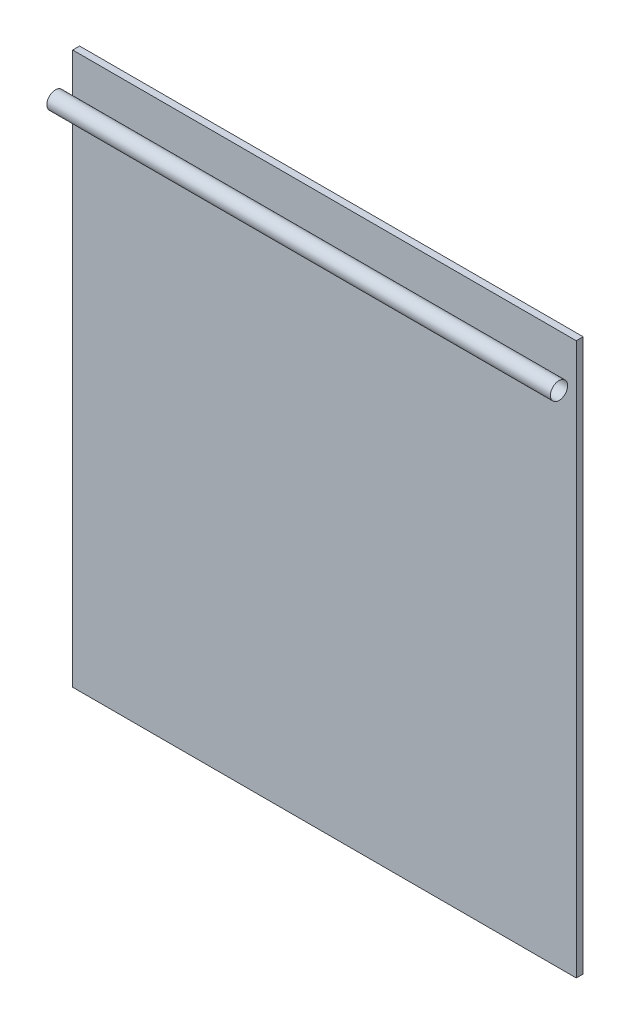
SolidWorks part; units mm, degrees
material "201 Annealed Stainless Steel (SS)"
ref_plane "Front Plane" through (0, 0, 0) normal (0, 0, 1) x (1, 0, 0)
ref_plane "Top Plane" through (0, 0, 0) normal (0, 1, 0) x (1, 0, 0)
ref_plane "Right Plane" through (0, 0, 0) normal (1, 0, 0) x (0, 0, -1)
sketch "Sketch1" plane through (0, 0, 0) normal (0, 0, 1) x (1, 0, 0)
  line L1 (-73, -80) -> (73, -80)
  line L2 (-73, -80) -> (-73, 80)
  line L3 (-73, 80) -> (73, 80)
  line L4 (73, -80) -> (73, 80)
  line L5 (-73, -80) -> (73, 80) construction
  line L6 (-73, 80) -> (73, -80) construction
  point P0 (0, 0)
  dimension "D1" = 146
  dimension "D2" = 160
extrude "Boss-Extrude1" add sketch "Sketch1" along normal blind 2
sketch "Sketch2" [suppressed] plane through (0, 0, 0) normal (0, 0, -1) x (-1, 0, 0)
  line L0 (61, 200) -> (61, -200) construction
  line L1 (-61, 314.7216) -> (-204.3993, 314.7216)
  line L2 (-61, 314.7216) -> (-61, -251.9618)
  line L3 (-61, -251.9618) -> (-204.3993, -251.9618)
  line L4 (-204.3993, 314.7216) -> (-204.3993, -251.9618)
  line L6 (61, 279.3211) -> (244.4765, 279.3211)
  line L7 (61, 279.3211) -> (61, -295.1839)
  line L8 (61, -295.1839) -> (244.4765, -295.1839)
  line L9 (244.4765, 279.3211) -> (244.4765, -295.1839)
  line L10 (-61, -200) -> (-61, -140) construction
  dimension "D1" = 122
extrude "Cut-Extrude1" [suppressed] cut sketch "Sketch2" against normal through all
sketch "Sketch3" plane through (73, 0, 0) normal (1, 0, 0) x (0, 0, -1)
  line L0 (-2, 80) -> (0, 80) construction
  line L1 (-2, 80) -> (-2, -80) construction
  circle A0 centre (-7, 70) radius 2.5
  point P2 (-7.932, 72.0042)
  dimension "D3" = 5
  dimension "D1" = 10
  dimension "D2" = 5
surface "Surface-Extrude1" sketch "Sketch3"
sketch "Sketch4" plane through (-73, 0, 0) normal (-1, 0, 0) x (0, 0, 1)
  line L1 (2, 80) -> (0, 80) construction
  line L2 (0, -80) -> (0, 80) construction
  point P0 (7.5, 76)
  dimension "D1" = 4
  dimension "D2" = 7.5
ref_axis "Axis1" through (-73, 76, 7.5) along (1, 0, 0)
sketch "Sketch5" [suppressed] plane through (0, 0, 0) normal (0, 0, -1) x (-1, 0, 0)
  line L0 (49, 80) -> (49, -80) construction
  line L1 (-49, 80) -> (49, 80)
  line L2 (-49, 80) -> (-49, 60.2594)
  line L3 (-49, 60.2594) -> (49, 60.2594)
  line L4 (49, 80) -> (49, 60.2594)
extrude "Cut-Extrude2" [suppressed] cut sketch "Sketch5" against normal blind 3
sketch "Sketch6" [suppressed] plane through (0, 0, 2) normal (0, 0, 1) x (1, 0, 0)
  line L0 (0, 0) -> (103.2002, 0) construction
  line L1 (-40, 80) -> (-40, 108.3319) construction
  line L2 (-40, 80) -> (-27.987, 80) construction
  line L3 (0, 0) -> (0, 138.3235) construction
  line L4 (40, 80) -> (27.987, 80) construction
  line L5 (40, 80) -> (40, 108.3319) construction
  line L6 (40, -80) -> (40, -108.3319) construction
  line L7 (40, -80) -> (27.987, -80) construction
  line L8 (-40, -80) -> (-27.987, -80) construction
  line L9 (-40, -80) -> (-40, -108.3319) construction
  circle A0 centre (-40, 80) radius 4.5
  circle A2 centre (-45.8, 85.8) radius 1.95
  circle A3 centre (-45.8, 74.2) radius 1.95
  circle A4 centre (-34.2, 74.2) radius 1.95
  circle A5 centre (-34.2, 85.8) radius 1.95
  circle A6 centre (34.2, 85.8) radius 1.95
  circle A7 centre (34.2, 74.2) radius 1.95
  circle A8 centre (45.8, 74.2) radius 1.95
  circle A9 centre (45.8, 85.8) radius 1.95
  circle A10 centre (40, 80) radius 4.5
  circle A11 centre (40, -80) radius 4.5
  circle A12 centre (45.8, -85.8) radius 1.95
  circle A13 centre (45.8, -74.2) radius 1.95
  circle A14 centre (34.2, -74.2) radius 1.95
  circle A15 centre (34.2, -85.8) radius 1.95
  circle A16 centre (-34.2, -85.8) radius 1.95
  circle A17 centre (-34.2, -74.2) radius 1.95
  circle A18 centre (-45.8, -74.2) radius 1.95
  circle A19 centre (-45.8, -85.8) radius 1.95
  circle A20 centre (-40, -80) radius 4.5
  circle A21 centre (-40, 80) radius 5.1 construction
  dimension "D1" = 9
  dimension "D3" = 3.9
extrude "Leandut_holes" [suppressed] cut sketch "Sketch6" against normal through all
chamfer "Chamfer1" [suppressed] distance 5 angle 45
sketch "Sketch7" plane through (0, 0, 2) normal (0, 0, 1) x (1, 0, 0)
  line L0 (73, 80) -> (-73, 80) construction
  line L1 (-23, -125) -> (23, -125)
  line L2 (-23, -125) -> (-23, 60)
  line L3 (-23, 60) -> (23, 60)
  line L4 (23, -125) -> (23, 60)
  line L5 (0, 0) -> (0, -66.8576) construction
  line L7 (-73, 80) -> (-73, -80) construction
  point P0 (0, 0)
  dimension "D1" = 20
  dimension "D2" = 50
  dimension "D3" = 46
  dimension "D4" = 125
extrude "Plunger-Window" [suppressed] cut sketch "Sketch7" against normal through all
sketch "Sketch8" [suppressed] plane through (0, 0, 2) normal (0, 0, 1) x (1, 0, 0)
  line L0 (106, 145) -> (56, 145) construction
  line L1 (-56, 125) -> (56, 125)
  line L2 (-56, 125) -> (-56, 145)
  line L3 (-56, 145) -> (56, 145)
  line L4 (56, 125) -> (56, 145)
  line L5 (56, -110) -> (56, 125) construction
extrude "Cut-Extrude3" [suppressed] cut sketch "Sketch8" against normal blind 5
